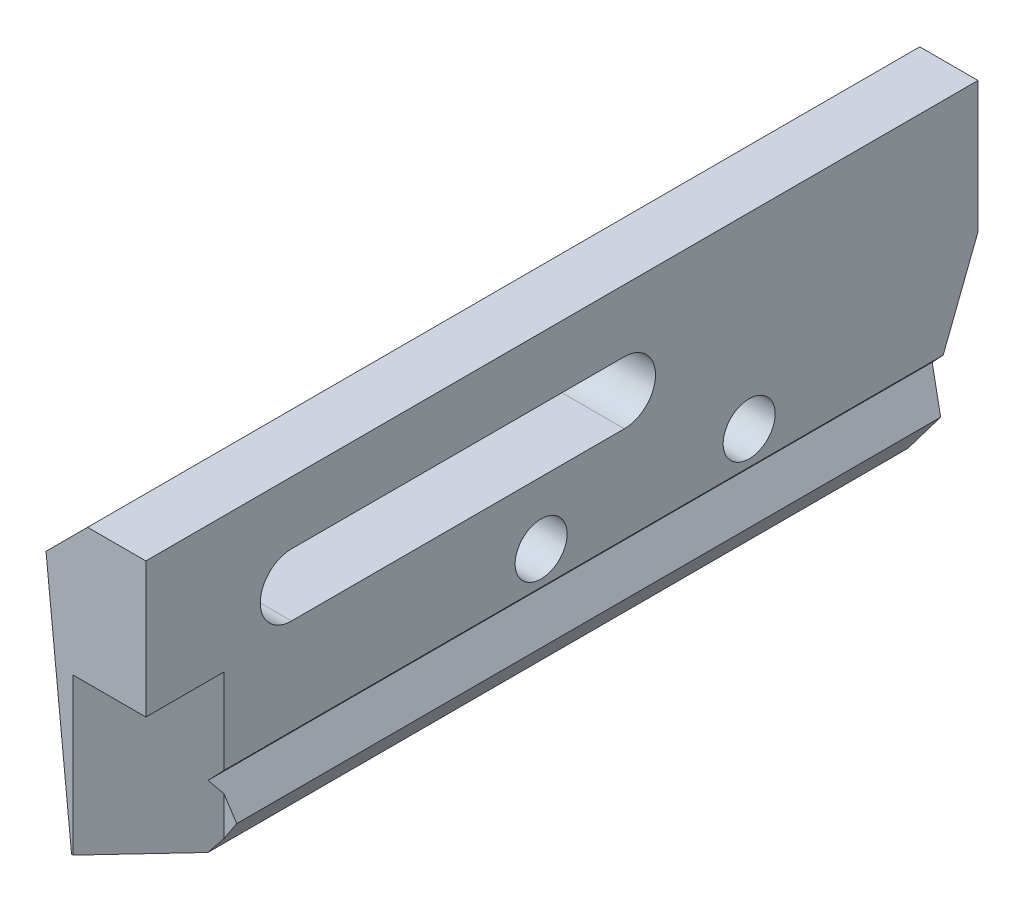
SolidWorks part; units mm, degrees
ref_plane "Plan de face" through (0, 0, 0) normal (0, 0, 1) x (1, 0, 0)
ref_plane "Plan de dessus" through (0, 0, 0) normal (0, 1, 0) x (1, 0, 0)
ref_plane "Plan de droite" through (0, 0, 0) normal (1, 0, 0) x (0, 0, -1)
sketch "Esquisse1" plane through (0, 0, 0) normal (0, 0, 1) x (1, 0, 0)
  line L0 (0, -2) -> (2, 0)
  line L1 (2, 0) -> (4.8, 0)
  line L3 (1.23, -14) -> (4.43, -14)
  line L4 (4.8, 0) -> (4.8, -10.6)
  line L6 (4.43, -11) -> (5.42, -12.5)
  line L7 (5.42, -12.5) -> (4.43, -14)
  line L8 (0, -2) -> (1.23, -14)
  line L9 (4.43, -11) -> (4.8, -10.6)
  point P0 (0, 0)
  dimension "D1" = 4.8
  dimension "D2" = 3.2
  dimension "D6" = 12
  dimension "D3" = 4.19
  dimension "D4" = 2.8
  dimension "D7" = 1.5
  dimension "D8" = 3
  dimension "D9" = 10.6
  dimension "D5" = 2
extrude "Boss.-Extru.1" add sketch "Esquisse1" along normal blind 40
sketch "Esquisse2" plane through (4.8, 0, 0) normal (1, 0, 0) x (0, 0, -1)
  line L0 (0, -10.6) -> (0, 0) construction
  line L1 (0, -14) -> (0, -6.3)
  line L2 (0, -6.3) -> (-3, -14)
  line L3 (-40, -14) -> (0, -14) construction
  line L4 (-3, -14) -> (0, -14)
  line L5 (-40, 0) -> (0, 0) construction
  dimension "D1" = 6.3
  dimension "D2" = 3
extrude "Enlèv. mat.-Extru.1" cut sketch "Esquisse2" against normal through all and the other way through all
ref_plane "Plan1" through (0, -6.5, 0) normal (0, 1, 0) x (-1, 0, 0)
sketch "Esquisse3" plane through (0, -6.5, 0) normal (0, 1, 0) x (-1, 0, 0)
  line L0 (-4.8, 40) -> (-2, 40) construction
  line L1 (-6.8, 40) -> (-1.3, 40)
  line L3 (-6.8, 40) -> (-6.8, 36.25)
  line L4 (-1.3, 40) -> (-4.8, 36.25)
  line L5 (-4.8, 36.25) -> (-6.8, 36.25)
  dimension "D1" = 3.5
  dimension "D2" = 3.75
  dimension "D3" = 2
extrude "Enlèv. mat.-Extru.3" cut sketch "Esquisse3" against normal blind 40
hole_wizard "Trou taraudé M31" positions "Esquisse5" profile "Esquisse4" tap size "M3" standard "ISO"
sketch "Esquisse5" plane through (4.8, 0, 0) normal (1, 0, 0) x (0, 0, -1)
  line L0 (0, -6.3) -> (0, 0) construction
  line L1 (-40, 0) -> (0, 0) construction
  point P0 (-11, -9)
  point P1 (-21, -9)
  dimension "D1" = 10
  dimension "D2" = 11
  dimension "D3" = 9
sketch "Esquisse4" plane through (4.8, -9, 11) normal (0, 1, 0) x (0, 0, -1)
  line L0 (0, 0) -> (0, 9.2511)
  line L1 (0, 9.2511) -> (1.25, 8.5)
  line L2 (1.25, 8.5) -> (1.25, 0)
  line L5 (1.25, 0) -> (0, 0)
  line L10 (0, 9.2511) -> (-1.25, 8.5) construction
  line L11 (0, -6.35) -> (0, 107.95) construction
  dimension "Diamètre du trou pour taraudage" = 2.5
  dimension "Profondeur du trou pour taraudage" = 8.5
  dimension "Angle de pointe" = 118
cosmetic thread "Filetage de perçage1" parameters "D1"=4.2106, "D2"=3
cosmetic thread "Filetage de perçage2" parameters "D1"=4.2106, "D2"=3
sketch "Esquisse6" plane through (4.8, 0, 0) normal (1, 0, 0) x (0, 0, -1)
  line L0 (-33, -4.5) -> (-17, -4.5) construction
  line L1 (-33, -3) -> (-17, -3)
  line L2 (-33, -6) -> (-17, -6)
  line L3 (-40, -6.5) -> (-40, 0) construction
  line L4 (-40, 0) -> (0, 0) construction
  arc A0 (-33, -3) -> (-33, -6) centre (-33, -4.5) ccw
  arc A1 (-17, -6) -> (-17, -3) centre (-17, -4.5) ccw
  point P2 (-25, -4.5)
  dimension "D1" = 1.5
  dimension "D3" = 7
  dimension "D2" = 16
  dimension "D4" = 3
extrude "Enlèv. mat.-Extru.4" cut sketch "Esquisse6" against normal blind 3.6
